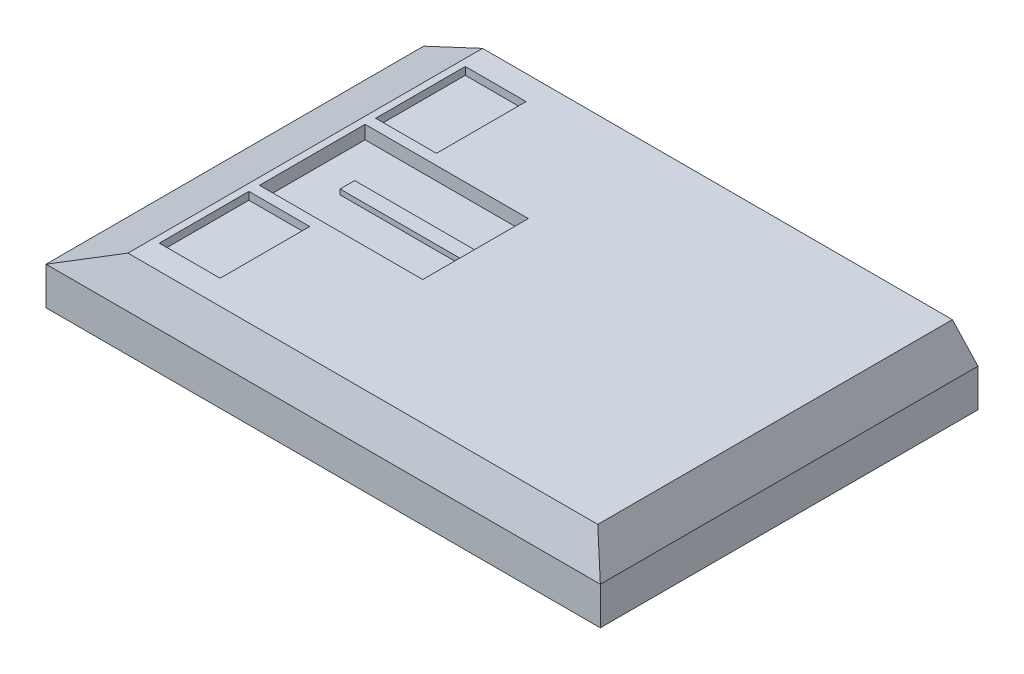
SolidWorks part; units mm, degrees
ref_plane "Front Plane" through (0, 0, 0) normal (0, 0, 1) x (1, 0, 0)
ref_plane "Top Plane" through (0, 0, 0) normal (0, 1, 0) x (1, 0, 0)
ref_plane "Right Plane" through (0, 0, 0) normal (1, 0, 0) x (0, 0, -1)
sketch "Sketch1" plane through (0, 0, 0) normal (0, 1, 0) x (1, 0, 0)
  line L1 (-219.964, -149.86) -> (0, -149.86)
  line L2 (-219.964, -149.86) -> (-219.964, 0)
  line L3 (-219.964, 0) -> (0, 0)
  line L4 (0, -149.86) -> (0, 0)
  dimension "D1" = 149.86
  dimension "D2" = 219.964
ref_plane "MiddleTop" through (0, 14.986, 0) normal (0, 1, 0) x (1, 0, 0)
sketch "Sketch2" plane through (0, 14.986, 0) normal (0, 1, 0) x (1, 0, 0)
  line L1 (0, 0) -> (-219.964, 0)
  line L2 (0, 0) -> (0, -149.86)
  line L3 (0, -149.86) -> (-219.964, -149.86)
  line L4 (-219.964, 0) -> (-219.964, -149.86)
extrude "Boss-Extrude1" add sketch "Sketch1" along normal blind 14.986
ref_plane "Plane2" through (0, 30.48, 0) normal (0, 1, 0) x (1, 0, 0)
sketch "Sketch3" plane through (0, 30.48, 0) normal (0, 1, 0) x (1, 0, 0)
  line L0 (0, -149.86) -> (-219.964, -149.86) construction
  line L1 (-192.024, -4.572) -> (-5.588, -4.572)
  line L2 (-192.024, -4.572) -> (-192.024, -145.288)
  line L3 (-192.024, -145.288) -> (-5.588, -145.288)
  line L4 (-5.588, -4.572) -> (-5.588, -145.288)
  line L5 (-219.964, 0) -> (-219.964, -149.86) construction
  line L6 (0, 0) -> (0, -149.86) construction
  dimension "D1" = 140.716
  dimension "D2" = 4.572
  dimension "D3" = 27.94
  dimension "D4" = 5.588
loft "Loft1" add profiles "Sketch2", "Sketch3" connector at (-219.964, 14.986, 149.86) connector at (-192.024, 30.48, 145.288)
sketch "Sketch4" plane through (0, 30.48, 0) normal (0, 1, 0) x (1, 0, 0)
  line L0 (-192.024, -145.288) -> (-5.588, -145.288) construction
  line L1 (-189.23, -135.636) -> (-165.1, -135.636)
  line L2 (-189.23, -135.636) -> (-189.23, -100.076)
  line L3 (-189.23, -100.076) -> (-165.1, -100.076)
  line L4 (-165.1, -135.636) -> (-165.1, -100.076)
  line L5 (-192.024, -4.572) -> (-192.024, -145.288) construction
  line L6 (-5.588, -4.572) -> (-192.024, -4.572) construction
  line L7 (-189.23, -49.784) -> (-165.1, -49.784)
  line L8 (-189.23, -49.784) -> (-189.23, -14.224)
  line L9 (-189.23, -14.224) -> (-165.1, -14.224)
  line L10 (-165.1, -49.784) -> (-165.1, -14.224)
  point P12 (-177.165, -14.224)
  dimension "D1" = 35.56
  dimension "D2" = 24.13
  dimension "D3" = 9.652
  dimension "D4" = 2.794
  dimension "D5" = 24.13
  dimension "D6" = 35.56
  dimension "D7" = 2.794
  dimension "D8" = 9.652
sketch "Sketch5" plane through (0, 30.48, 0) normal (0, 1, 0) x (1, 0, 0)
  line L0 (-189.23, -100.076) -> (-165.1, -100.076) construction
  line L1 (-189.23, -95.885) -> (-124.46, -95.885)
  line L2 (-189.23, -95.885) -> (-189.23, -53.975)
  line L3 (-189.23, -53.975) -> (-124.46, -53.975)
  line L4 (-124.46, -95.885) -> (-124.46, -53.975)
  line L5 (-192.024, -4.572) -> (-192.024, -145.288) construction
  dimension "D1" = 41.91
  dimension "D2" = 4.191
  dimension "D3" = 2.794
  dimension "D4" = 64.77
extrude "Cut-Extrude1" cut sketch "Sketch4" against normal blind 3.048
extrude "Cut-Extrude2" cut sketch "Sketch5" against normal blind 5.334
ref_plane "Plane3" through (0, 25.146, 0) normal (0, 1, 0) x (1, 0, 0)
sketch "Sketch6" plane through (0, 25.146, 0) normal (0, 1, 0) x (1, 0, 0)
  line L0 (-189.23, -53.975) -> (-189.23, -95.885) construction
  line L1 (-175.26, -72.0598) -> (-124.46, -72.0598)
  line L2 (-175.26, -72.0598) -> (-175.26, -77.851)
  line L3 (-175.26, -77.851) -> (-124.46, -77.851)
  line L4 (-124.46, -72.0598) -> (-124.46, -77.851)
  line L5 (-189.23, -95.885) -> (-124.46, -95.885) construction
  dimension "D1" = 50.8
  dimension "D2" = 13.97
  dimension "D3" = 5.7912
  dimension "D4" = 18.034
extrude "Boss-Extrude2" add sketch "Sketch6" along normal blind 2.032
sketch "Sketch10" plane through (0, 30.48, 0) normal (0, 1, 0) x (1, 0, 0)
  line L6 (-219.964, -149.86) -> (0, -149.86) construction
  line L9 (-144.145, -145.1356) -> (-145.923, -145.1356)
  line L10 (-145.923, -145.1356) -> (-145.923, -139.8016)
  line L11 (-145.923, -139.8016) -> (-143.383, -139.8016)
  line L12 (-143.383, -139.8016) -> (-143.383, -136.5758)
  line L13 (-143.383, -136.5758) -> (-24.003, -136.5758)
  line L14 (-24.003, -136.5758) -> (-24.003, -139.8016)
  line L15 (-24.003, -139.8016) -> (-21.463, -139.8016)
  line L16 (-21.463, -139.8016) -> (-21.463, -145.1356)
  line L17 (-21.463, -145.1356) -> (-23.241, -145.1356)
  line L21 (-23.241, -149.86) -> (-144.145, -149.86)
  line L22 (-144.145, -145.1356) -> (-144.145, -149.86)
  line L23 (-23.241, -145.1356) -> (-23.241, -149.86)
  line L24 (0, -149.86) -> (0, 0) construction
  line L25 (-219.964, -74.93) -> (-5.588, -74.93) construction
  line L27 (-219.964, 0) -> (-219.964, -149.86) construction
  line L28 (-5.588, -145.288) -> (-5.588, -4.572) construction
  line L29 (-21.463, -4.7244) -> (-23.241, -4.7244)
  line L30 (-21.463, -10.0584) -> (-21.463, -4.7244)
  line L31 (-24.003, -10.0584) -> (-21.463, -10.0584)
  line L32 (-24.003, -13.2842) -> (-24.003, -10.0584)
  line L33 (-143.383, -13.2842) -> (-24.003, -13.2842)
  line L34 (-143.383, -10.0584) -> (-143.383, -13.2842)
  line L35 (-145.923, -10.0584) -> (-143.383, -10.0584)
  line L36 (-145.923, -4.7244) -> (-145.923, -10.0584)
  line L37 (-144.145, -4.7244) -> (-145.923, -4.7244)
  line L38 (-144.145, -4.7244) -> (-144.145, 0)
  line L39 (-23.241, 0) -> (-144.145, 0)
  line L40 (-23.241, -4.7244) -> (-23.241, 0)
  dimension "D1" = 13.2842
  dimension "D2" = 5.334
  dimension "D3" = 3.2258
  dimension "D4" = 2.54
  dimension "D5" = 124.46
  dimension "D6" = 3.2258
  dimension "D7" = 2.54
  dimension "D8" = 1.778
  dimension "D9" = 5.334
  dimension "D10" = 21.463
  dimension "D11" = 1.778
